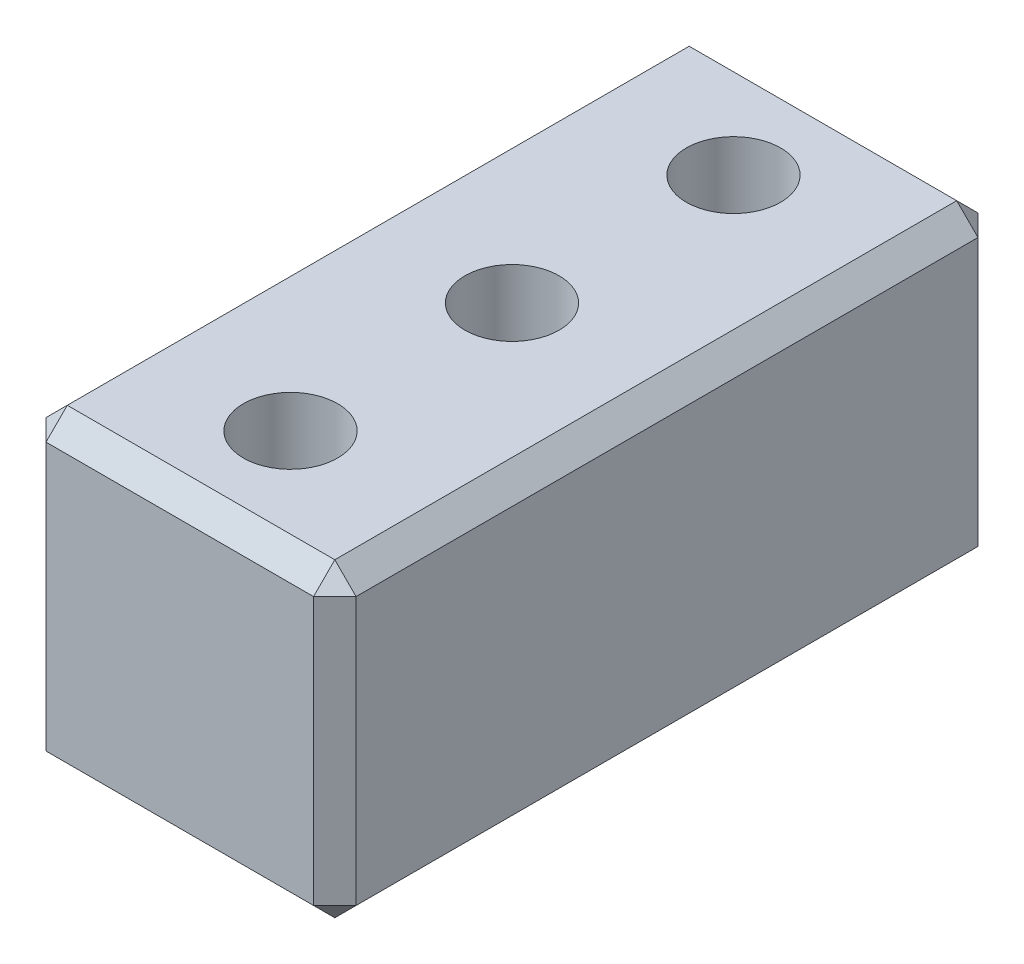
SolidWorks part; units mm, degrees
material "PET"
ref_plane "Front" through (0, 0, 0) normal (0, 0, 1) x (1, 0, 0)
ref_plane "Top" through (0, 0, 0) normal (0, 1, 0) x (1, 0, 0)
ref_plane "Right" through (0, 0, 0) normal (1, 0, 0) x (0, 0, -1)
sketch "Sketch1" plane through (0, 0, 0) normal (0, 0, 1) x (1, 0, 0)
  line L1 (11.1125, -11.1125) -> (-11.1125, -11.1125)
  line L2 (11.1125, -11.1125) -> (11.1125, 11.1125)
  line L3 (11.1125, 11.1125) -> (-11.1125, 11.1125)
  line L4 (-11.1125, -11.1125) -> (-11.1125, 11.1125)
  line L5 (11.1125, -11.1125) -> (-11.1125, 11.1125) construction
  line L6 (11.1125, 11.1125) -> (-11.1125, -11.1125) construction
  point P0 (0, 0)
  dimension "D1" = 22.225
extrude "Boss-Extrude1" add sketch "Sketch1" along normal mid plane 47.625
hole_wizard "1/4 Clearance Hole1" positions "Sketch2" profile "Sketch3" hole size "1/4" standard "ANSI Inch" end condition through all
sketch "Sketch2" plane through (0, 11.1125, 0) normal (0, 1, 0) x (1, 0, 0)
  line L0 (0, 15.875) -> (0, -15.875) construction
  point P1 (0, 15.875)
  point P2 (0, -15.875)
  point P8 (0, 0)
  dimension "D1" = 15.875
sketch "Sketch3" plane through (0, 11.1125, -15.875) normal (1, 0, 0) x (0, 0, 1)
  line L0 (0, 0) -> (0, 22.225)
  line L1 (0, 22.225) -> (3.3782, 22.225)
  line L2 (3.3782, 22.225) -> (3.3782, 0)
  line L5 (3.3782, 0) -> (0, 0)
  line L11 (0, -6.35) -> (0, 107.95) construction
  dimension "Thru Hole Dia." = 6.7564
  dimension "Thru Hole Depth" = 22.225
chamfer "Chamfer1" distance 1.524 angle 45 12 edges at (-11.1125, 11.1125, 0) (-11.1125, 0, 23.8125) (-11.1125, -11.1125, 0) (-11.1125, 0, -23.8125) (0, 11.1125, -23.8125) (11.1125, 0, -23.8125) (0, -11.1125, -23.8125) (11.1125, -11.1125, 0) (0, -11.1125, 23.8125) (11.1125, 0, 23.8125) (0, 11.1125, 23.8125) (11.1125, 11.1125, 0)
